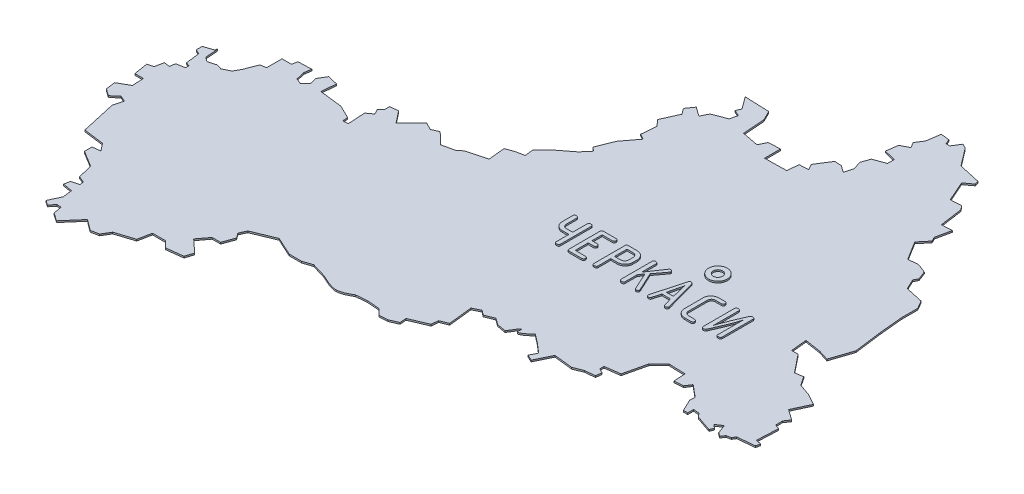
SolidWorks part; units mm, degrees
ref_plane "Спереди" through (0, 0, 0) normal (0, 0, 1) x (1, 0, 0)
ref_plane "Сверху" through (0, 0, 0) normal (0, 1, 0) x (1, 0, 0)
ref_plane "Справа" through (0, 0, 0) normal (1, 0, 0) x (0, 0, -1)
sketch "Эскиз1" plane through (0, 0, 0) normal (0, 1, 0) x (1, 0, 0)
  line B0 (-10045.3673, 2871.7646) -> (-10031.095, 2888.6099)
  line B1 (-10031.095, 2888.6099) -> (-10017.4577, 2887.3069)
  line B2 (-10017.4577, 2887.3069) -> (-10012.2584, 2860.0705)
  line B3 (-10012.2584, 2860.0705) -> (-9986.9701, 2842.5419)
  line B4 (-9986.9701, 2842.5419) -> (-9940.8869, 2895.7676)
  line B5 (-9940.8869, 2895.7676) -> (-9906.5055, 2869.8012)
  line B6 (-9906.5055, 2869.8012) -> (-9881.1817, 2874.9904)
  line B7 (-9881.1817, 2874.9904) -> (-9865.6038, 2900.9569)
  line B8 (-9865.6038, 2900.9569) -> (-9807.2169, 2919.7452)
  line B9 (-9807.2169, 2919.7452) -> (-9798.7714, 2961.9575)
  line B10 (-9798.7714, 2961.9575) -> (-9756.5718, 2961.9575)
  line B11 (-9756.5718, 2961.9575) -> (-9737.7733, 2941.8534)
  line B12 (-9737.7733, 2941.8534) -> (-9684.5653, 2948.338)
  line B13 (-9684.5653, 2948.338) -> (-9676.1249, 2974.2917)
  line B14 (-9676.1249, 2974.2917) -> (-9716.9986, 3011.9269)
  line B15 (-9716.9986, 3011.9269) -> (-9691.6951, 3045.6429)
  line B16 (-9691.6951, 3045.6429) -> (-9664.446, 3045.6429)
  line B17 (-9664.446, 3045.6429) -> (-9650.8265, 3083.306)
  line B18 (-9650.8265, 3083.306) -> (-9662.4902, 3098.8864)
  line B19 (-9662.4902, 3098.8864) -> (-9652.1143, 3120.9488)
  line B20 (-9652.1143, 3120.9488) -> (-9581.3702, 3150.1512)
  line B21 (-9581.3702, 3150.1512) -> (-9521.7005, 3122.8919)
  line B22 (-9521.7005, 3122.8919) -> (-9482.0892, 3122.8919)
  line B23 (-9482.0892, 3122.8919) -> (-9452.8894, 3132.6328)
  line B24 (-9452.8894, 3132.6328) -> (-9406.7909, 3118.9981)
  line B25 (-9303.004, 3115.7443) -> (-9267.2941, 3118.9981)
  line B26 (-9267.2941, 3118.9981) -> (-9226.4281, 3115.7443)
  line B27 (-9226.4281, 3115.7443) -> (-9207.5711, 3096.9433)
  line B28 (-9207.5711, 3096.9433) -> (-9181.625, 3098.8864)
  line B29 (-9181.625, 3098.8864) -> (-9154.3835, 3110.5983)
  line B30 (-9154.3835, 3110.5983) -> (-9156.3368, 3131.3247)
  line B31 (-9156.3368, 3131.3247) -> (-9099.87, 3155.3404)
  line B32 (-9099.87, 3155.3404) -> (-9097.899, 3177.4003)
  line B33 (-9097.899, 3177.4003) -> (-9072.6031, 3187.7991)
  line B34 (-9072.6031, 3187.7991) -> (-9081.0461, 3264.3623)
  line B35 (-9081.0461, 3264.3623) -> (-9057.0355, 3276.0488)
  line B36 (-9057.0355, 3276.0488) -> (-9042.08, 3264.3623)
  line B37 (-9042.08, 3264.3623) -> (-9012.9055, 3276.0488)
  line B38 (-9012.9055, 3276.0488) -> (-8992.1512, 3261.1162)
  line B39 (-8992.1512, 3261.1162) -> (-8963.5889, 3255.932)
  line B40 (-8905.2044, 3294.8753) -> (-8876.6345, 3272.7976)
  line B41 (-8876.6345, 3272.7976) -> (-8847.4347, 3247.4967)
  line B42 (-8847.4347, 3247.4967) -> (-8859.1161, 3224.784)
  line B43 (-8859.1161, 3224.784) -> (-8840.2846, 3216.3436)
  line B44 (-8840.2846, 3216.3436) -> (-8815.004, 3267.6135)
  line B45 (-8815.004, 3267.6135) -> (-8755.2911, 3261.1162)
  line B46 (-8755.2911, 3261.1162) -> (-8726.0633, 3272.7976)
  line B47 (-8726.0633, 3272.7976) -> (-8693.6326, 3276.0488)
  line B48 (-8693.6326, 3276.0488) -> (-8691.6743, 3294.8753)
  line B49 (-8691.6743, 3294.8753) -> (-8705.9364, 3301.9949)
  line B50 (-8705.9364, 3301.9949) -> (-8705.9364, 3315.6398)
  line B51 (-8705.9364, 3315.6398) -> (-8657.9304, 3322.1066)
  line B52 (-8657.9304, 3322.1066) -> (-8641.0698, 3394.1512)
  line B53 (-8641.0698, 3394.1512) -> (-8608.6315, 3426.5794)
  line B54 (-8608.6315, 3426.5794) -> (-8555.4109, 3424.6541)
  line B55 (-8555.4109, 3424.6541) -> (-8553.4602, 3387.0087)
  line B56 (-8553.4602, 3387.0087) -> (-8524.9156, 3388.9518)
  line B57 (-8524.9156, 3388.9518) -> (-8512.5839, 3407.7834)
  line B58 (-8512.5839, 3407.7834) -> (-8473.6534, 3375.3323)
  line B59 (-8473.6534, 3375.3323) -> (-8474.9564, 3358.4515)
  line B60 (-8474.9564, 3358.4515) -> (-8456.7649, 3320.829)
  line B61 (-8456.7649, 3320.829) -> (-8443.1683, 3320.829)
  line B62 (-8443.1683, 3320.829) -> (-8443.1683, 3339.6301)
  line B63 (-8443.1683, 3339.6301) -> (-8424.3189, 3337.687)
  line B64 (-8424.3189, 3337.687) -> (-8413.9583, 3326.0157)
  line B65 (-8413.9583, 3326.0157) -> (-8362.6706, 3308.4872)
  line B66 (-8362.6706, 3308.4872) -> (-8357.456, 3320.829)
  line B67 (-8357.456, 3320.829) -> (-8369.1628, 3330.5521)
  line B68 (-8369.1628, 3330.5521) -> (-8349.0537, 3344.197)
  line B69 (-8349.0537, 3344.197) -> (-8338.6498, 3315.6398)
  line B70 (-8338.6498, 3315.6398) -> (-8326.9938, 3307.1968)
  line B71 (-8326.9938, 3307.1968) -> (-8318.5584, 3318.8656)
  line B72 (-8318.5584, 3318.8656) -> (-8304.2608, 3322.1066)
  line B73 (-8304.2608, 3322.1066) -> (-8297.7507, 3332.4851)
  line B74 (-8297.7507, 3332.4851) -> (-8243.2601, 3337.687)
  line B75 (-8243.2601, 3337.687) -> (-8240.014, 3351.3065)
  line B76 (-8240.014, 3351.3065) -> (-8256.9126, 3354.5577)
  line B77 (-8256.9126, 3354.5577) -> (-8253.6487, 3422.7033)
  line B78 (-8253.6487, 3422.7033) -> (-8268.5865, 3427.8926)
  line B79 (-8268.5865, 3427.8926) -> (-8268.5865, 3450.6002)
  line B80 (-8268.5865, 3450.6002) -> (-8256.9126, 3467.4708)
  line B81 (-8256.9126, 3467.4708) -> (-8290.6718, 3491.4865)
  line B82 (-8290.6718, 3491.4865) -> (-8265.3378, 3545.9899)
  line B83 (-8265.3378, 3545.9899) -> (-8299.7116, 3564.8113)
  line B84 (-8299.7116, 3564.8113) -> (-8338.6498, 3578.4358)
  line B85 (-8338.6498, 3578.4358) -> (-8357.456, 3607.0134)
  line B86 (-8357.456, 3607.0134) -> (-8382.8052, 3602.4566)
  line B87 (-8382.8052, 3602.4566) -> (-8428.8605, 3660.1984)
  line B88 (-8428.8605, 3660.1984) -> (-8449.6351, 3660.1984)
  line B89 (-8449.6351, 3660.1984) -> (-8454.8142, 3711.4886)
  line B90 (-8454.8142, 3711.4886) -> (-8401.5859, 3703.0457)
  line B91 (-8401.5859, 3703.0457) -> (-8369.1628, 3692.6393)
  line B92 (-8369.1628, 3692.6393) -> (-8345.7999, 3762.7408)
  line B93 (-8345.7999, 3762.7408) -> (-8357.456, 3851.6458)
  line B94 (-8357.456, 3851.6458) -> (-8364.6391, 3926.2787)
  line B95 (-8364.6391, 3926.2787) -> (-8364.6391, 3979.5044)
  line B96 (-8364.6391, 3979.5044) -> (-8379.587, 4004.8028)
  line B97 (-8379.587, 4004.8028) -> (-8435.9928, 4017.1268)
  line B98 (-8435.9928, 4017.1268) -> (-8451.5757, 4049.5804)
  line B99 (-8451.5757, 4049.5804) -> (-8444.4357, 4063.2126)
  line B100 (-8444.4357, 4063.2126) -> (-8454.8142, 4090.4617)
  line B101 (-8454.8142, 4090.4617) -> (-8485.3196, 4102.1305)
  line B102 (-8485.3196, 4102.1305) -> (-8516.4701, 4098.892)
  line B103 (-8516.4701, 4098.892) -> (-8553.4602, 4158.5845)
  line B104 (-8553.4602, 4158.5845) -> (-8528.1618, 4189.0899)
  line B105 (-8528.1618, 4189.0899) -> (-8535.3271, 4202.7094)
  line B106 (-8535.3271, 4202.7094) -> (-8524.9156, 4250.751)
  line B107 (-8524.9156, 4250.751) -> (-8558.6824, 4248.7977)
  line B108 (-8558.6824, 4248.7977) -> (-8569.0354, 4322.1377)
  line B109 (-8569.0354, 4322.1377) -> (-8579.4139, 4334.4567)
  line B110 (-8579.4139, 4334.4567) -> (-8613.8207, 4332.511)
  line B111 (-8613.8207, 4332.511) -> (-8642.383, 4397.3877)
  line B112 (-8642.383, 4397.3877) -> (-8617.0567, 4416.232)
  line B113 (-8617.0567, 4416.232) -> (-8620.2876, 4427.9058)
  line B114 (-8620.2876, 4427.9058) -> (-8690.4043, 4443.4811)
  line B115 (-8690.4043, 4443.4811) -> (-8733.2134, 4499.9377)
  line B116 (-8733.2134, 4499.9377) -> (-8747.4679, 4507.0751)
  line B117 (-8747.4679, 4507.0751) -> (-8763.7163, 4481.1036)
  line B118 (-8763.7163, 4481.1036) -> (-8775.3977, 4481.1036)
  line B119 (-8775.3977, 4481.1036) -> (-8782.5224, 4496.6915)
  line B120 (-8782.5224, 4496.6915) -> (-8809.7893, 4499.9377)
  line B121 (-8809.7893, 4499.9377) -> (-8816.2816, 4455.8229)
  line B122 (-8816.2816, 4455.8229) -> (-8831.8315, 4431.8149)
  line B123 (-8831.8315, 4431.8149) -> (-8821.4886, 4414.2762)
  line B124 (-8821.4886, 4414.2762) -> (-8847.4347, 4400.6389)
  line B125 (-8847.4347, 4400.6389) -> (-8852.6569, 4363.654)
  line B126 (-8852.6569, 4363.654) -> (-8815.004, 4354.576)
  line B127 (-8815.004, 4354.576) -> (-8815.004, 4332.511)
  line B128 (-8815.004, 4332.511) -> (-8852.6569, 4318.8814)
  line B129 (-8852.6569, 4318.8814) -> (-8862.3521, 4291.6373)
  line B130 (-8862.3521, 4291.6373) -> (-8853.9015, 4264.3704)
  line B131 (-8853.9015, 4264.3704) -> (-8861.0592, 4237.1213)
  line B132 (-8861.0592, 4237.1213) -> (-8883.0912, 4252.6788)
  line B133 (-8883.0912, 4252.6788) -> (-8905.2044, 4253.9869)
  line B134 (-8905.2044, 4253.9869) -> (-8934.3967, 4207.924)
  line B135 (-8934.3967, 4207.924) -> (-8924.0004, 4189.0899)
  line B136 (-8924.0004, 4189.0899) -> (-8953.2282, 4187.8021)
  line B137 (-8953.2282, 4187.8021) -> (-8956.4566, 4151.4522)
  line B138 (-8956.4566, 4151.4522) -> (-9026.5123, 4150.1543)
  line B139 (-9026.5123, 4150.1543) -> (-9026.5123, 4201.4318)
  line B140 (-9026.5123, 4201.4318) -> (-9064.1576, 4199.4861)
  line B141 (-9064.1576, 4199.4861) -> (-9075.8747, 4175.4679)
  line B142 (-9075.8747, 4175.4679) -> (-9129.0623, 4185.8387)
  line B143 (-9129.0623, 4185.8387) -> (-9134.2591, 4255.9249)
  line B144 (-9134.2591, 4255.9249) -> (-9149.1867, 4286.4354)
  line B145 (-9149.1867, 4286.4354) -> (-9227.7057, 4289.6993)
  line B146 (-9227.7057, 4289.6993) -> (-9199.1536, 4250.751)
  line B147 (-9199.1536, 4250.751) -> (-9205.6534, 4235.1706)
  line B148 (-9205.6534, 4235.1706) -> (-9186.7965, 4226.7378)
  line B149 (-9186.7965, 4226.7378) -> (-9192.0212, 4202.7094)
  line B150 (-9192.0212, 4202.7094) -> (-9236.1334, 4185.8387)
  line B151 (-9236.1334, 4185.8387) -> (-9248.4524, 4161.8357)
  line B152 (-9248.4524, 4161.8357) -> (-9277.6624, 4182.6053)
  line B153 (-9277.6624, 4182.6053) -> (-9294.5153, 4158.5845)
  line B154 (-9294.5153, 4158.5845) -> (-9280.9263, 4139.7885)
  line B155 (-9280.9263, 4139.7885) -> (-9304.9293, 4086.5552)
  line B156 (-9304.9293, 4086.5552) -> (-9287.4465, 4066.446)
  line B157 (-9287.4465, 4066.446) -> (-9291.2794, 4018.4095)
  line B158 (-9291.2794, 4018.4095) -> (-9273.7686, 4008.6788)
  line B159 (-9273.7686, 4008.6788) -> (-9310.1439, 3960.6703)
  line B160 (-9310.1439, 3960.6703) -> (-9332.214, 3906.1619)
  line B161 (-9332.214, 3906.1619) -> (-9319.8671, 3895.7707)
  line B162 (-9319.8671, 3895.7707) -> (-9341.9193, 3869.817)
  line B163 (-9341.9193, 3869.817) -> (-9387.9594, 3834.1249)
  line B164 (-9387.9594, 3834.1249) -> (-9420.4384, 3801.6688)
  line B165 (-9420.4384, 3801.6688) -> (-9417.1999, 3774.4349)
  line B166 (-9417.1999, 3774.4349) -> (-9444.4541, 3769.2305)
  line B167 (-9444.4541, 3769.2305) -> (-9470.4179, 3759.4946)
  line B168 (-9470.4179, 3759.4946) -> (-9465.2135, 3706.2943)
  line B169 (-9465.2135, 3706.2943) -> (-9528.1801, 3689.4186)
  line B170 (-9528.1801, 3689.4186) -> (-9543.7376, 3677.0818)
  line B171 (-9543.7376, 3677.0818) -> (-9582.691, 3668.6287)
  line B172 (-9582.691, 3668.6287) -> (-9619.6658, 3704.3411)
  line B173 (-9619.6658, 3704.3411) -> (-9641.7257, 3694.5926)
  line B174 (-9641.7257, 3694.5926) -> (-9664.446, 3706.2943)
  line B175 (-9664.446, 3706.2943) -> (-9713.7601, 3656.9701)
  line B176 (-9713.7601, 3656.9701) -> (-9744.2528, 3695.9057)
  line B177 (-9744.2528, 3695.9057) -> (-9770.2192, 3692.6393)
  line B178 (-9770.2192, 3692.6393) -> (-9770.2192, 3675.7864)
  line B179 (-9770.2192, 3675.7864) -> (-9781.8931, 3665.4003)
  line B180 (-9781.8931, 3665.4003) -> (-9773.4653, 3648.5297)
  line B181 (-9773.4653, 3648.5297) -> (-9792.2613, 3634.9051)
  line B182 (-9792.2613, 3634.9051) -> (-9789.033, 3579.7312)
  line B183 (-9789.033, 3579.7312) -> (-9805.9215, 3578.4358)
  line B184 (-9805.9215, 3578.4358) -> (-9807.2169, 3595.3268)
  line B185 (-9807.2169, 3595.3268) -> (-9850.0463, 3616.0939)
  line B186 (-9850.0463, 3616.0939) -> (-9922.0757, 3624.5216)
  line B187 (-9922.0757, 3624.5216) -> (-9918.1691, 3670.5896)
  line B188 (-9918.1691, 3670.5896) -> (-9950.6202, 3679.0325)
  line B189 (-9950.6202, 3679.0325) -> (-9966.2056, 3653.0661)
  line B190 (-9966.2056, 3653.0661) -> (-9961.0037, 3629.7159)
  line B191 (-9961.0037, 3629.7159) -> (-9977.882, 3614.1254)
  line B192 (-9977.882, 3614.1254) -> (-9995.3978, 3621.2805)
  line B193 (-9995.3978, 3621.2805) -> (-10001.8952, 3649.82)
  line B194 (-10001.8952, 3649.82) -> (-9998.649, 3671.885)
  line B195 (-9998.649, 3671.885) -> (-10041.4684, 3670.5896)
  line B196 (-10041.4684, 3670.5896) -> (-10044.7272, 3653.0661)
  line B197 (-10044.7272, 3653.0661) -> (-10075.2199, 3653.0661)
  line B198 (-10075.2199, 3653.0661) -> (-10075.2199, 3603.752)
  line B199 (-10075.2199, 3603.752) -> (-10094.0413, 3600.4983)
  line B200 (-10094.0413, 3600.4983) -> (-10109.5962, 3559.6398)
  line B201 (-10109.5962, 3559.6398) -> (-10121.3006, 3538.855)
  line B202 (-10121.3006, 3538.855) -> (-10145.3188, 3527.1812)
  line B203 (-10145.3188, 3527.1812) -> (-10162.1615, 3532.378)
  line B204 (-10162.1615, 3532.378) -> (-10188.128, 3525.2203)
  line B205 (-10188.128, 3525.2203) -> (-10201.7576, 3535.6216)
  line B206 (-10201.7576, 3535.6216) -> (-10205.0063, 3576.4902)
  line B207 (-10205.0063, 3576.4902) -> (-10206.9494, 3576.4902)
  line B208 (-10206.9494, 3576.4902) -> (-10206.9494, 3570.0005)
  line B209 (-10206.9494, 3570.0005) -> (-10237.4675, 3559.6398)
  line B210 (-10237.4675, 3559.6398) -> (-10237.4675, 3540.8108)
  line B211 (-10237.4675, 3540.8108) -> (-10222.517, 3533.6785)
  line B212 (-10222.517, 3533.6785) -> (-10217.3329, 3489.5409)
  line B213 (-10217.3329, 3489.5409) -> (-10205.0063, 3484.3644)
  line B214 (-10205.0063, 3484.3644) -> (-10205.0063, 3473.9682)
  line B215 (-10205.0063, 3473.9682) -> (-10232.2706, 3468.7713)
  line B216 (-10232.2706, 3468.7713) -> (-10234.2036, 3451.9032)
  line B217 (-10234.2036, 3451.9032) -> (-10253.0224, 3453.8463)
  line B218 (-10253.0224, 3453.8463) -> (-10258.2142, 3426.5794)
  line B219 (-10258.2142, 3426.5794) -> (-10277.028, 3421.3902)
  line B220 (-10277.028, 3421.3902) -> (-10269.8855, 3376.6201)
  line B221 (-10269.8855, 3376.6201) -> (-10242.6618, 3376.6201)
  line B222 (-10242.6618, 3376.6201) -> (-10240.6882, 3339.6301)
  line B223 (-10240.6882, 3339.6301) -> (-10277.028, 3318.8656)
  line B224 (-10277.028, 3318.8656) -> (-10273.1519, 3288.3653)
  line B225 (-10273.1519, 3288.3653) -> (-10251.0666, 3272.7976)
  line B226 (-10251.0666, 3272.7976) -> (-10229.022, 3291.6292)
  line B227 (-10229.022, 3291.6292) -> (-10210.1828, 3283.1634)
  line B228 (-10210.1828, 3283.1634) -> (-10218.6334, 3252.0204)
  line B229 (-10218.6334, 3252.0204) -> (-10193.3248, 3139.7651)
  line B230 (-10193.3248, 3139.7651) -> (-10128.4303, 3131.3247)
  line B231 (-10128.4303, 3131.3247) -> (-10109.5962, 3107.3242)
  line B232 (-10109.5962, 3107.3242) -> (-10134.9124, 3104.0705)
  line B233 (-10134.9124, 3104.0705) -> (-10134.9124, 3080.0548)
  line B234 (-10134.9124, 3080.0548) -> (-10084.3029, 3048.9068)
  line B235 (-10084.3029, 3048.9068) -> (-10071.9636, 3001.5307)
  line B236 (-10071.9636, 3001.5307) -> (-10051.8468, 2993.1081)
  line B237 (-10051.8468, 2993.1081) -> (-10049.9088, 2980.7789)
  line B238 (-10049.9088, 2980.7789) -> (-10073.9296, 2974.2917)
  line B239 (-10073.9296, 2974.2917) -> (-10077.1681, 2955.4602)
  line B240 (-10077.1681, 2955.4602) -> (-10046.6881, 2950.2887)
  line B241 (-10046.6881, 2950.2887) -> (-10042.7688, 2919.7452)
  line B242 (-10042.7688, 2919.7452) -> (-10060.2872, 2882.1253)
  line B243 (-10060.2872, 2882.1253) -> (-10045.3673, 2871.7646)
  spline B244 degree 2 poles (-9406.7909, 3118.9981) (-9362.7067, 3096.9433) (-9345.8284, 3098.8864) knots 0.100402 0.100402 0.100402 0.104418 0.104418 0.104418
  spline B245 degree 2 poles (-9345.8284, 3098.8864) (-9328.2922, 3100.1767) (-9303.004, 3115.7443) knots 0.104418 0.104418 0.104418 0.108434 0.108434 0.108434
  spline B246 degree 2 poles (-8963.5889, 3255.932) (-8937.625, 3300.0645) (-8940.8711, 3279.9299) knots 0.168675 0.168675 0.168675 0.172691 0.172691 0.172691
  spline B247 degree 2 poles (-8940.8711, 3279.9299) (-8944.7472, 3259.1781) (-8905.2044, 3294.8753) knots 0.172691 0.172691 0.172691 0.176707 0.176707 0.176707
sketch_block_instance "Блок6-1"
sketch_block "Блок6"
extrude "Бобышка-Вытянуть1" add sketch "Эскиз1" along normal blind 5 contours B246 B247 B40 B41 B42 B43 B44 B45 B46 B47 B48 B49 B50 B51 B52 B53 B54 B55 B56 B57 B58 B59 B60 B61 B62 B63 B64 B65 B66 B67 B68 B69 B70 B71 B72 B73 B74 B75 B76 B77 B78 B79 B80 B81 B82 B83 B84 B85 B86 B87 B88 region at (-9199.143, 0, -3597.8164)
sketch "Эскиз2" plane through (0, 0, 0) normal (0, 1, 0) x (1, 0, 0)
  line L0 (-9176.9728, 3574.4961) -> (-8590.1547, 3574.4961) construction
  circle A0 centre (-8776.0801, 3750.5638) radius 15
  circle A1 centre (-8776.0801, 3750.5638) radius 30
  text T0 "<b>ЧЕРКАСИ</b>" font "GOST Type AU" height 110
  dimension "D1" = 30
  dimension "D2" = 60
extrude "Бобышка-Вытянуть2" add sketch "Эскиз2" along normal blind 10
scale "Масштаб1" scale about centroid uniform scaling yes scale factor 0.05
